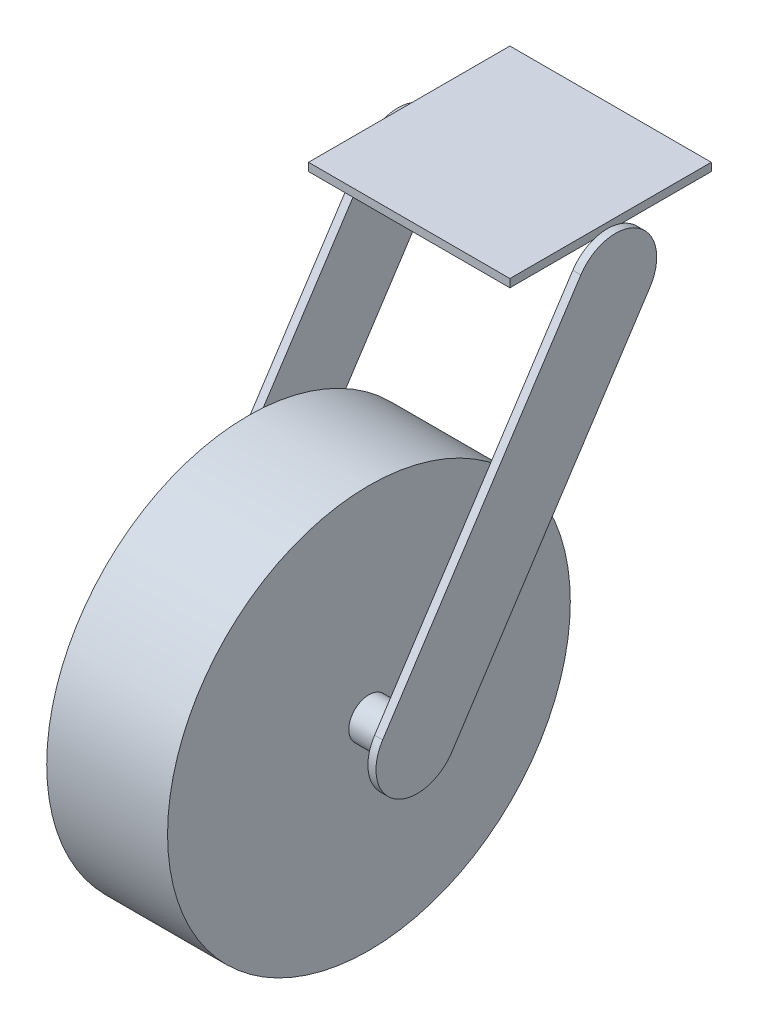
SolidWorks part; units mm, degrees
ref_plane "Front Plane" through (0, 0, 0) normal (0, 0, 1) x (1, 0, 0)
ref_plane "Top Plane" through (0, 0, 0) normal (0, 1, 0) x (1, 0, 0)
ref_plane "Right Plane" through (0, 0, 0) normal (1, 0, 0) x (0, 0, -1)
sketch "Sketch1" plane through (0, 0, 0) normal (1, 0, 0) x (0, 0, -1)
  circle A0 centre (0, 0) radius 100
  dimension "D1" = 200
extrude "Boss-Extrude2" add sketch "Sketch1" along normal blind 30 and the other way blind 30 contours A0
sketch "Sketch2" plane through (30, 0, 0) normal (1, 0, 0) x (0, 0, -1)
  circle A0 centre (0, 0) radius 10
  dimension "D1" = 20
extrude "Boss-Extrude3" add sketch "Sketch2" along normal blind 20
sketch "Sketch3" plane through (-30, 0, 0) normal (-1, 0, 0) x (0, 0, 1)
  circle A0 centre (0, 0) radius 10
  dimension "D1" = 20
extrude "Boss-Extrude4" add sketch "Sketch3" along normal blind 20
sketch "Sketch5" plane through (-50, 0, 0) normal (-1, 0, 0) x (0, 0, 1)
  line L0 (0, 0) -> (-98.4001, 150.723) construction
  line L1 (-17.1736, -11.2119) -> (-115.5738, 139.5111)
  line L2 (17.1736, 11.2119) -> (-81.2265, 161.9348)
  arc A0 (-17.1736, -11.2119) -> (17.1736, 11.2119) centre (0, 0) ccw
  arc A1 (-81.2265, 161.9348) -> (-115.5738, 139.5111) centre (-98.4001, 150.723) ccw
  point P2 (-49.2001, 75.3615)
  dimension "D1" = 180
extrude "Boss-Extrude5" add sketch "Sketch5" along normal blind 4
mirror "Mirror1" about plane through (0, 0, 0) normal (1, 0, 0) of "Boss-Extrude5"
sketch3d "3DSketch2" plane through (0, 0, 0) normal (0, 0, 1) x (1, 0, 0)
  dimension "D1" = 170
sketch "Sketch9" plane through (0, 170, 0) normal (0, 1, 0) x (1, 0, 0)
  line L1 (0, 0) -> (-50, 0)
  line L2 (0, 0) -> (0, 150)
  line L3 (0, 150) -> (-50, 150)
  line L4 (-50, 0) -> (-50, 150)
  dimension "D1" = 150
  dimension "D2" = 50
sketch "Sketch10" plane through (0, 170, 0) normal (0, 1, 0) x (1, 0, 0)
  line L1 (-50, 150) -> (50, 150)
  line L2 (-50, 150) -> (-50, 50)
  line L3 (-50, 50) -> (50, 50)
  line L4 (50, 150) -> (50, 50)
  dimension "D1" = 100
  dimension "D2" = 100
extrude "Boss-Extrude6" add sketch "Sketch10" along normal blind 4
